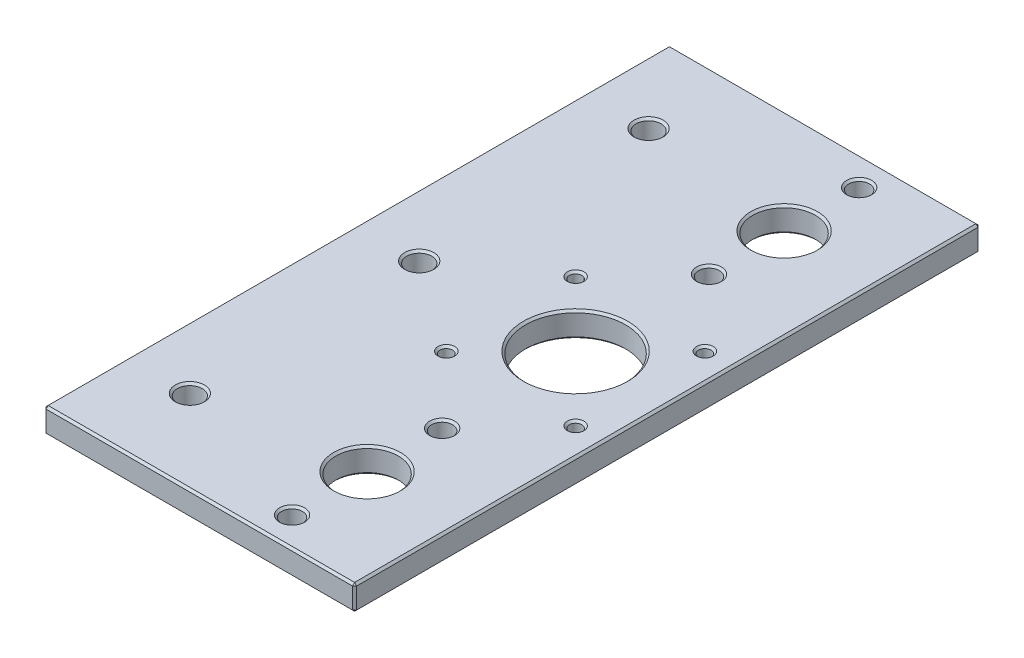
SolidWorks part; units mm, degrees
ref_plane "Alzado" through (0, 0, 0) normal (0, 0, 1) x (1, 0, 0)
ref_plane "Planta" through (0, 0, 0) normal (0, 1, 0) x (1, 0, 0)
ref_plane "Vista lateral" through (0, 0, 0) normal (1, 0, 0) x (0, 0, -1)
sketch "Croquis1" plane through (0, 0, 0) normal (0, 1, 0) x (1, 0, 0)
  line L1 (-39.7283, 73.9586) -> (34.7717, 73.9586)
  line L2 (-39.7283, 73.9586) -> (-39.7283, -76.0414)
  line L3 (-39.7283, -76.0414) -> (34.7717, -76.0414)
  line L4 (34.7717, 73.9586) -> (34.7717, -76.0414)
  circle A0 centre (-2.7283, 14.4586) radius 1.5
  circle A1 centre (28.2717, 14.4586) radius 1.5
  circle A2 centre (-2.7283, -16.5414) radius 1.5
  circle A3 centre (28.2717, -16.5414) radius 1.5
  circle A4 centre (-24.7283, 53.9586) radius 3
  circle A5 centre (-24.7283, -56.0414) radius 3
  circle A6 centre (12.7717, -1.0414) radius 12
  circle A7 centre (-24.7283, -1.0414) radius 3
  circle A8 centre (12.7717, -51.0414) radius 7.5
  circle A9 centre (12.7717, 48.9586) radius 7.5
  circle A10 centre (12.7717, 66.9586) radius 2.5
  circle A11 centre (12.7717, 30.9586) radius 2.5
  circle A12 centre (12.7717, -33.0414) radius 2.5
  circle A13 centre (12.7717, -69.0414) radius 2.5
  dimension "D7" = 3
  dimension "D8" = 6
  dimension "D9" = 6
  dimension "D10" = 3
  dimension "D11" = 3
  dimension "D12" = 3
  dimension "D17" = 75
  dimension "D16" = 24
  dimension "D19" = 6
  dimension "D20" = 15
  dimension "D21" = 15
  dimension "D24" = 5
  dimension "D25" = 5
  dimension "D28" = 5
  dimension "D29" = 5
  dimension "D1" = 150
  dimension "D2" = 22
  dimension "D3" = 31
  dimension "D4" = 31
  dimension "D5" = 15.5
  dimension "D6" = 6.5
  dimension "D13" = 20
  dimension "D14" = 15
  dimension "D15" = 20
  dimension "D18" = 15.5
  dimension "D22" = 50
  dimension "D23" = 50
  dimension "D26" = 18
  dimension "D27" = 18
  dimension "D30" = 18
  dimension "D31" = 18
extrude "Saliente-Extruir1" add sketch "Croquis1" along normal blind 6
chamfer "Chaflán1" distance 0.5 angle 45 40 edges at (28.2717, 0, 18.0414) (28.2717, 0, -12.9586) (-2.7283, 0, -12.9586) (-2.7283, 0, 18.0414) (28.2717, 6, 18.0414) (28.2717, 6, -12.9586) (-39.7283, 3, -73.9586) (-39.7283, 3, 76.0414) (34.7717, 3, 76.0414) (-2.4783, 0, 76.0414) (34.7717, 0, 1.0414) (-39.7283, 0, 1.0414) (-2.4783, 0, -73.9586) (34.7717, 3, -73.9586) (-2.4783, 6, -73.9586) (34.7717, 6, 1.0414) (-2.4783, 6, 76.0414) (-39.7283, 6, 1.0414) (-2.7283, 6, -12.9586) (-2.7283, 6, 18.0414) (-24.7283, 0, 59.0414) (-24.7283, 0, -50.9586) (-24.7283, 6, 59.0414) (-24.7283, 6, -50.9586) (12.7717, 0, 13.0414) (12.7717, 6, 13.0414) (12.7717, 0, -41.4586) (-24.7283, 0, 4.0414) (12.7717, 0, 58.5414) (12.7717, 6, -41.4586) (-24.7283, 6, 4.0414) (12.7717, 6, 58.5414) (12.7717, 0, 71.5414) (12.7717, 0, -28.4586) (12.7717, 0, -64.4586) (12.7717, 0, 35.5414) (12.7717, 6, 71.5414) (12.7717, 6, -28.4586) (12.7717, 6, -64.4586) (12.7717, 6, 35.5414)
